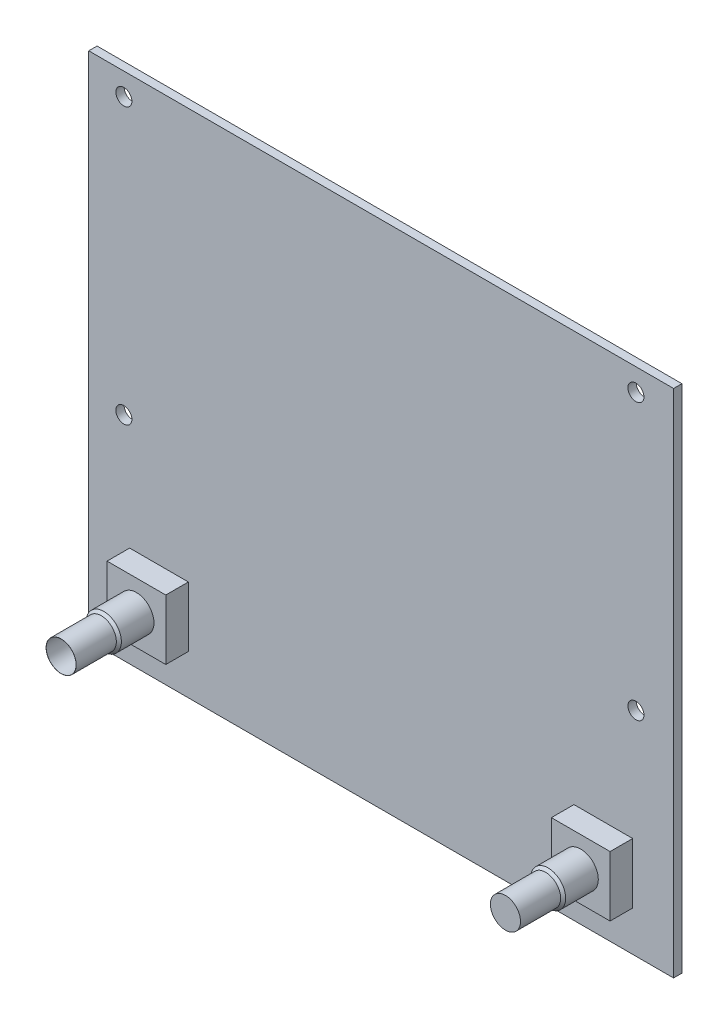
SolidWorks part; units mm, degrees
ref_plane "Front Plane" through (0, 0, 0) normal (0, 0, 1) x (1, 0, 0)
ref_plane "Top Plane" through (0, 0, 0) normal (0, 1, 0) x (1, 0, 0)
ref_plane "Right Plane" through (0, 0, 0) normal (1, 0, 0) x (0, 0, -1)
sketch "Sketch1" plane through (0, 0, 0) normal (0, 0, 1) x (1, 0, 0)
  line L1 (-58.2701, 50.8698) -> (58.2701, 50.8698)
  line L2 (-58.2701, 50.8698) -> (-58.2701, -50.8698)
  line L3 (-58.2701, -50.8698) -> (58.2701, -50.8698)
  line L4 (58.2701, 50.8698) -> (58.2701, -50.8698)
  line L5 (-58.2701, 50.8698) -> (58.2701, -50.8698) construction
  line L6 (-58.2701, -50.8698) -> (58.2701, 50.8698) construction
  circle A0 centre (-51.2699, 46.4502) radius 1.6002
  circle A1 centre (50.7695, 46.4502) radius 1.6002
  circle A2 centre (50.7695, -8.4493) radius 1.6002
  circle A3 centre (-51.2699, -8.4493) radius 1.6002
  point P0 (0, 0)
  dimension "D3" = 3.2004
  dimension "D6" = 3.2004
  dimension "D7" = 3.2004
  dimension "D8" = 3.2004
  dimension "D1" = 101.7397
  dimension "D2" = 116.5403
  dimension "D4" = 7.0002
  dimension "D5" = 4.4196
  dimension "D9" = 7.5006
  dimension "D10" = 54.8996
extrude "Boss-Extrude1" add sketch "Sketch1" along normal blind 1.6561
sketch "Sketch2" plane through (0, 0, 1.6561) normal (0, 0, 1) x (1, 0, 0)
  line L0 (0, 50.8698) -> (0, -50.8698) construction
  line L1 (-50.1193, -42.8688) -> (-38.42, -42.8688)
  line L2 (-50.1193, -42.8688) -> (-50.1193, -30.8699)
  line L3 (-50.1193, -30.8699) -> (-38.42, -30.8699)
  line L4 (-38.42, -42.8688) -> (-38.42, -30.8699)
  line L5 (58.2701, 50.8698) -> (-58.2701, 50.8698) construction
  line L36 (-58.2701, -50.8698) -> (58.2701, -50.8698) construction
  line L37 (50.1193, -30.8699) -> (38.42, -30.8699)
  line L38 (38.42, -42.8688) -> (38.42, -30.8699)
  line L39 (50.1193, -42.8688) -> (38.42, -42.8688)
  line L40 (50.1193, -42.8688) -> (50.1193, -30.8699)
  dimension "D1" = 8.1509
  dimension "D2" = 8.001
  dimension "D3" = 11.6992
  dimension "D4" = 11.999
  dimension "D5" = 8.1509
  dimension "D6" = 8.001
  dimension "D7" = 11.6992
  dimension "D8" = 11.999
extrude "Boss-Extrude2" add sketch "Sketch2" along normal blind 4.5
sketch "Sketch3" plane through (0, 0, 6.1561) normal (0, 0, 1) x (1, 0, 0)
  line L0 (-44.2697, -42.8688) -> (-44.2697, -30.8699) construction
  line L1 (-50.1193, -42.8688) -> (-38.42, -42.8688) construction
  line L2 (-38.42, -30.8699) -> (-50.1193, -30.8699) construction
  line L3 (-50.1193, -36.8694) -> (-38.42, -36.8694) construction
  line L4 (-50.1193, -30.8699) -> (-50.1193, -42.8688) construction
  line L5 (-38.42, -42.8688) -> (-38.42, -30.8699) construction
  line L6 (38.42, -42.8688) -> (50.1193, -30.8699) construction
  line L7 (50.1193, -42.8688) -> (38.42, -30.8699) construction
  circle A0 centre (-44.2697, -36.8694) radius 3.5
  circle A1 centre (44.2697, -36.8694) radius 3.5
  point P16 (-44.2697, -36.8694)
  point P26 (44.2697, -36.8694)
  dimension "D1" = 7
  dimension "D2" = 7
extrude "Boss-Extrude3" add sketch "Sketch3" along normal blind 7
chamfer "Chamfer1" distance 0.5 angle 45 2 edges at (-40.7697, -36.8694, 13.1561) (47.7697, -36.8694, 13.1561)
sketch "Sketch5" plane through (0, 0, 13.1561) normal (0, 0, 1) x (1, 0, 0)
  circle A0 centre (44.2697, -36.8694) radius 3 construction
  circle A1 centre (-44.2697, -36.8694) radius 3 construction
  circle A2 centre (44.2697, -36.8694) radius 3
  circle A3 centre (-44.2697, -36.8694) radius 3
  circle A4 centre (-44.2697, -36.8694) radius 2.9781
  dimension "D1" = 6
  dimension "D2" = 5.9563
extrude "Boss-Extrude4" add sketch "Sketch5" along normal blind 8
sketch "Sketch6" plane through (0, 0, 0) normal (0, 0, -1) x (-1, 0, 0)
  line L0 (-58.2701, 50.8698) -> (58.2701, 50.8698) construction
  line L1 (-37.7952, 36.4553) -> (39.2557, 36.4553)
  line L2 (-37.7952, 36.4553) -> (-37.7952, 15.8052)
  line L3 (-37.7952, 15.8052) -> (39.2557, 15.8052)
  line L4 (39.2557, 36.4553) -> (39.2557, 15.8052)
  dimension "D1" = 14.4145
  dimension "D2" = 19.0144
  dimension "D3" = 77.0509
  dimension "D4" = 20.6502
extrude "Cut-Extrude1" cut sketch "Sketch6" against normal blind 1
